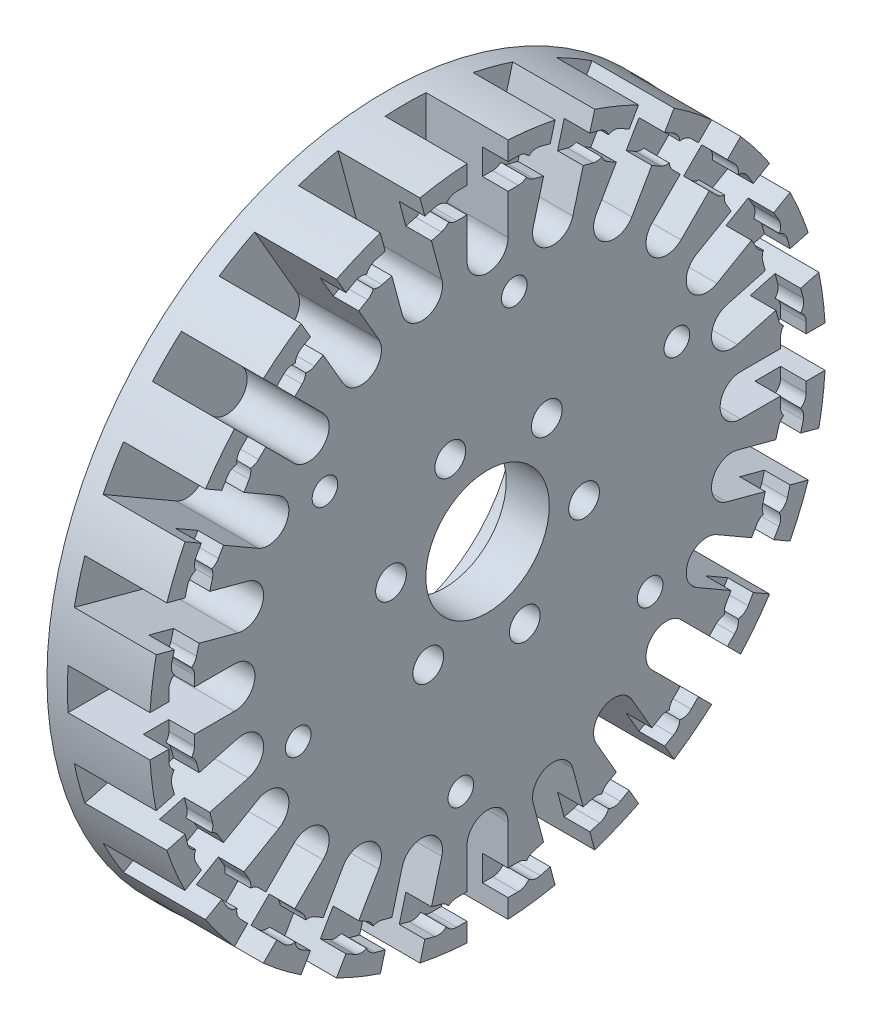
SolidWorks part; units mm, degrees
ref_plane "Front Plane" through (0, 0, 0) normal (0, 0, 1) x (1, 0, 0)
ref_plane "Top Plane" through (0, 0, 0) normal (0, 1, 0) x (1, 0, 0)
ref_plane "Right Plane" through (0, 0, 0) normal (1, 0, 0) x (0, 0, -1)
sketch "Sketch1" plane through (0, 0, 0) normal (1, 0, 0) x (0, 0, -1)
  circle A0 centre (0, 0) radius 33
  circle A1 centre (0, 0) radius 6.025
  dimension "D1" = 66
  dimension "D2" = 12.05
extrude "Boss-Extrude1" add sketch "Sketch1" along normal blind 10
sketch "Sketch2" plane through (10, 0, 0) normal (1, 0, 0) x (0, 0, -1)
  line L0 (-2, 33) -> (2, 33)
  line L1 (2, 33) -> (2, 24.7)
  line L2 (-2, 24.7) -> (-2, 33)
  arc A0 (2, 24.7) -> (-2, 24.7) centre (0, 24.7) cw
  circle A1 centre (0, 0) radius 33 construction
  dimension "D1" = 4
  dimension "D2" = 8.3
extrude "Cut-Extrude1" cut sketch "Sketch2" against normal blind 8
sketch "Sketch3" plane through (10, 0, 0) normal (1, 0, 0) x (0, 0, -1)
  line L0 (-3, 29.85) -> (3, 29.85) construction
  line L1 (-3, 31.1) -> (3, 31.1)
  line L2 (-3, 28.6) -> (3, 28.6)
  arc A0 (-3, 31.1) -> (-3, 28.6) centre (-3, 29.85) ccw
  arc A1 (3, 28.6) -> (3, 31.1) centre (3, 29.85) ccw
  arc A2 (-2, 24.7) -> (2, 24.7) centre (0, 24.7) ccw construction
  point P2 (0, 29.85)
  dimension "D1" = 1.25
  dimension "D2" = 5.15
  dimension "D3" = 6
extrude "Cut-Extrude2" cut sketch "Sketch3" against normal blind 2.5
pattern_circular "CirPattern1" count 24 over 360 about axis through (10, 0, 0) along (1, 0, 0) of "Cut-Extrude1", "Cut-Extrude2"
hole_wizard "Tap Drill for M3x0.5 Tap1" positions "Sketch6" profile "Sketch5" hole size "M3x0.5" standard "ANSI Metric" end condition up to next
sketch "Sketch6" plane through (10, 0, 0) normal (1, 0, 0) x (0, 0, -1)
  line L0 (2.6105, 19.8289) -> (0, 0) construction
  line L1 (0, 0) -> (6.025, 0) construction
  circle A2 centre (0, 0) radius 6.025 construction
  point P0 (2.6105, 19.8289)
  dimension "D1" = 82.5
  dimension "D2" = 20
sketch "Sketch5" plane through (10, 19.8289, -2.6105) normal (0, 1, 0) x (0, 0, -1)
  line L0 (0, 0) -> (0, 10.001)
  line L1 (0, 10.001) -> (1.25, 10.001)
  line L2 (1.25, 10.001) -> (1.25, 0)
  line L5 (1.25, 0) -> (0, 0)
  line L11 (0, -6.35) -> (0, 107.95) construction
  dimension "Thru Hole Dia." = 2.5
  dimension "Thru Hole Depth" = 10.001
pattern_circular "CirPattern2" count 6 over 360 about axis through (10, 0, 0) along (1, 0, 0) of "Tap Drill for M3x0.5 Tap1"
sketch "Sketch7" plane through (0, 0, 0) normal (-1, 0, 0) x (0, 0, 1)
  circle A0 centre (0, 0) radius 12.71
  dimension "D1" = 25.42
extrude "Cut-Extrude3" cut sketch "Sketch7" against normal offset from surface (5.8 mm away) 4.2 up to face at (10, 7.6537, -19.7276)
sketch "Sketch11" plane through (10, 0, 0) normal (1, 0, 0) x (0, 0, -1)
  line L0 (0, 0) -> (-10.5081, 0) construction
  line L1 (-3.6355, 8.7769) -> (0, 0) construction
  circle A0 centre (-3.6355, 8.7769) radius 1.5
  dimension "D1" = 3
  dimension "D2" = 9.5
  dimension "D3" = 67.5
extrude "Cut-Extrude4" cut sketch "Sketch11" against normal up to next
pattern_circular "CirPattern3" count 6 over 360 about axis through (10, 0, 0) along (1, 0, 0) of "Cut-Extrude4"
